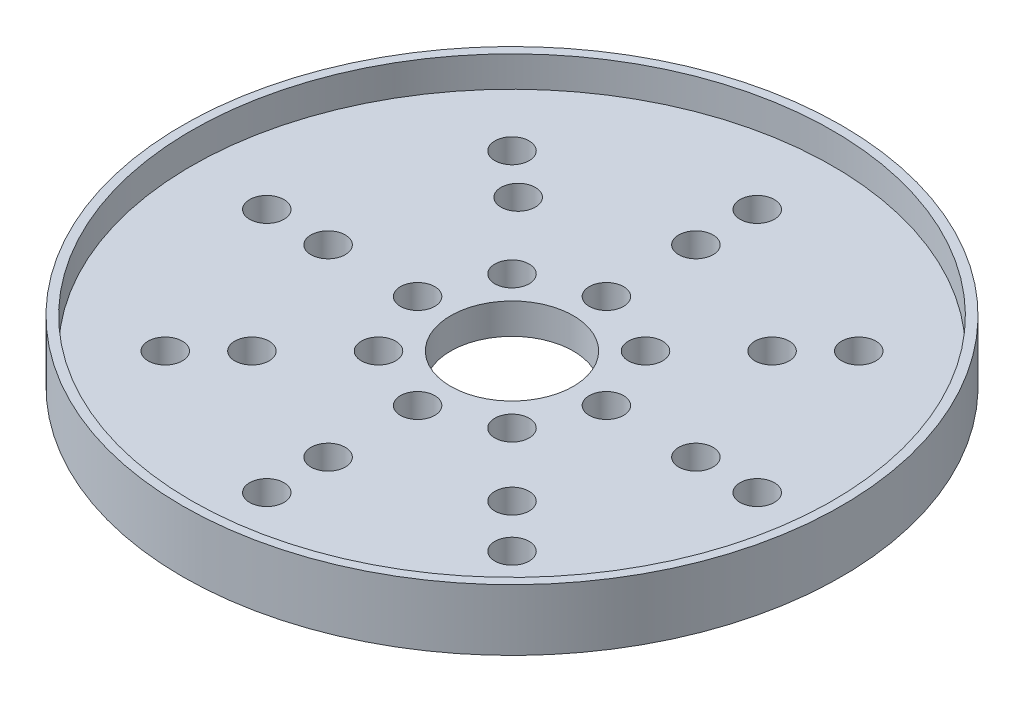
SolidWorks part; units mm, degrees
ref_plane "Front Plane" through (0, 0, 0) normal (0, 0, 1) x (1, 0, 0)
ref_plane "Top Plane" through (0, 0, 0) normal (0, 1, 0) x (1, 0, 0)
ref_plane "Right Plane" through (0, 0, 0) normal (1, 0, 0) x (0, 0, -1)
sketch "Sketch1" plane through (0, 0, 0) normal (0, 1, 0) x (1, 0, 0)
  circle A0 centre (0, 0) radius 34.1376
  dimension "D1" = 68.2752
extrude "Boss-Extrude1" add sketch "Sketch1" along normal blind 6.35
sketch "Sketch2" plane through (0, 6.35, 0) normal (0, 1, 0) x (1, 0, 0)
  circle A0 centre (0, 0) radius 33.2105
extrude "Cut-Extrude3" cut sketch "Sketch2" against normal blind 3.175
sketch "Sketch3" plane through (0, 3.175, 0) normal (0, 1, 0) x (1, 0, 0)
  line L0 (0, 0) -> (0, 25.4) construction
  line L1 (0, 0) -> (0, -25.4) construction
  line L2 (0, 0) -> (25.4, 0) construction
  line L3 (0, 0) -> (-25.4, 0) construction
  line L4 (0, 0) -> (17.9605, 17.9605) construction
  line L5 (0, 0) -> (-17.9605, 17.9605) construction
  line L6 (0, 0) -> (-17.9605, -17.9605) construction
  line L7 (0, 0) -> (17.9605, -17.9605) construction
  circle A0 centre (0, 0) radius 6.35
  circle A1 centre (25.4, 0) radius 1.778
  circle A2 centre (17.9605, 17.9605) radius 1.778
  circle A3 centre (0, 25.4) radius 1.778
  circle A4 centre (-17.9605, 17.9605) radius 1.778
  circle A5 centre (-25.4, 0) radius 1.778
  circle A6 centre (-17.9605, -17.9605) radius 1.778
  circle A7 centre (0, -25.4) radius 1.778
  circle A8 centre (17.9605, -17.9605) radius 1.778
  dimension "D1" = 12.7
  dimension "D2" = 3.556
  dimension "D3" = 3.556
  dimension "D4" = 3.556
  dimension "D5" = 3.556
  dimension "D6" = 3.556
  dimension "D7" = 3.556
  dimension "D8" = 3.556
  dimension "D9" = 3.556
extrude "Cut-Extrude4" cut sketch "Sketch3" against normal blind 3.175 contours A0
extrude "Cut-Extrude5" cut sketch "Sketch3<3>" against normal blind 3.175
sketch "Sketch3<3>" plane through (0, 3.175, 0) normal (0, 1, 0) x (1, 0, 0) same geometry as "Sketch3"
sketch "Sketch6" plane through (0, 3.175, 0) normal (0, 1, 0) x (1, 0, 0)
  line L0 (0, 0) -> (0, 19.05) construction
  line L1 (0, 0) -> (19.05, 0) construction
  line L2 (0, 0) -> (-19.05, 0) construction
  line L3 (0, 0) -> (0, -19.05) construction
  line L4 (0, 0) -> (13.4704, 13.4704) construction
  line L5 (0, 0) -> (-13.4704, -13.4704) construction
  line L6 (0, 0.6386) -> (-13.4704, 14.109) construction
  line L7 (0, 0) -> (13.4704, -13.4704) construction
  circle A0 centre (0, 19.05) radius 1.778
  circle A1 centre (-13.4704, 14.109) radius 1.778
  circle A2 centre (-19.05, 0) radius 1.778
  circle A3 centre (-13.4704, -13.4704) radius 1.778
  circle A4 centre (0, -19.05) radius 1.778
  circle A5 centre (13.4704, -13.4704) radius 1.778
  circle A6 centre (19.05, 0) radius 1.778
  circle A7 centre (13.4704, 13.4704) radius 1.778
extrude "Cut-Extrude6" cut sketch "Sketch6" against normal blind 3.175
sketch "Sketch8" plane through (0, 3.175, 0) normal (0, 1, 0) x (1, 0, 0)
  line L0 (0, 0) -> (9.779, 0) construction
  line L1 (0, 0) -> (-9.779, 0) construction
  line L2 (0, 0) -> (0, 9.779) construction
  line L3 (0, 0) -> (0, -9.779) construction
  line L4 (0, 0) -> (6.9148, 6.9148) construction
  line L5 (0, 0) -> (-6.9148, 6.9148) construction
  line L6 (0, 0) -> (-6.9148, -6.9148) construction
  line L7 (0, 0) -> (6.9148, -6.9148) construction
  circle A0 centre (9.779, 0) radius 1.778
  circle A1 centre (6.9148, 6.9148) radius 1.778
  circle A2 centre (0, 9.779) radius 1.778
  circle A3 centre (-6.9148, 6.9148) radius 1.778
  circle A4 centre (-9.779, 0) radius 1.778
  circle A5 centre (-6.9148, -6.9148) radius 1.778
  circle A6 centre (0, -9.779) radius 1.778
  circle A7 centre (6.9148, -6.9148) radius 1.778
extrude "Cut-Extrude7" cut sketch "Sketch8" against normal blind 3.175
